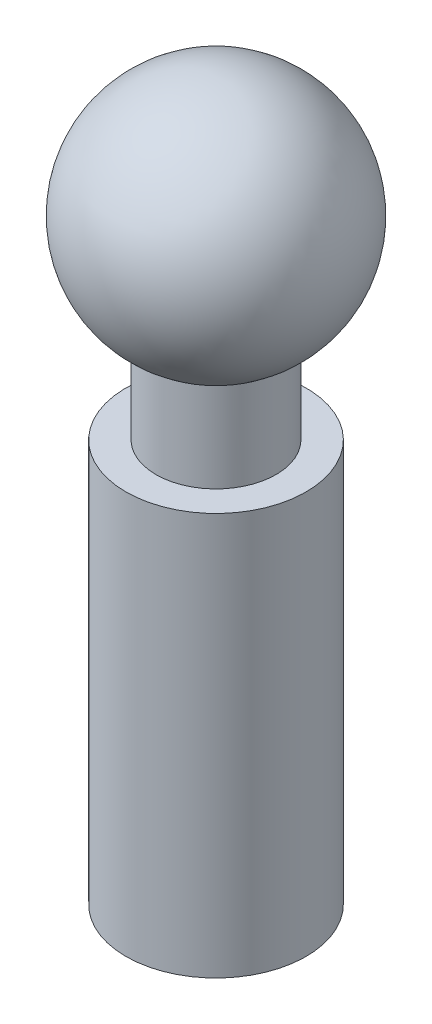
SolidWorks part; units mm, degrees
ref_plane "Front Plane" through (0, 0, 0) normal (0, 0, 1) x (1, 0, 0)
ref_plane "Top Plane" through (0, 0, 0) normal (0, 1, 0) x (1, 0, 0)
ref_plane "Right Plane" through (0, 0, 0) normal (1, 0, 0) x (0, 0, -1)
ref_axis "Axis1" through (0, 73.1826, 0) along (0, -1, 0)
sketch "Sketch1" plane through (0, 0, 0) normal (0, 1, 0) x (1, 0, 0)
  circle A0 centre (0, 0) radius 9.525
  dimension "D1" = 19.05
extrude "Boss-Extrude1" add sketch "Sketch1" along normal blind 42.545
sketch "Sketch2" plane through (0, 0, 0) normal (1, 0, 0) x (0, 0, -1)
  line L0 (-6.35, 42.545) -> (-6.35, 52.07)
  line L1 (0, 73.1826) -> (0, -3.4849) construction
  line L2 (0, 75.7685) -> (0, 42.545)
  line L3 (0, 42.545) -> (-6.35, 42.545)
  line L4 (9.525, 42.545) -> (-9.525, 42.545) construction
  arc A0 (0, 75.7685) -> (-6.35, 52.07) centre (0, 63.0685) ccw
  dimension "D1" = 12.7
  dimension "D3" = 0
  dimension "D2" = 6.35
  dimension "D4" = 9.525
revolve "Revolve1" add sketch "Sketch2" angle 360 about L2
